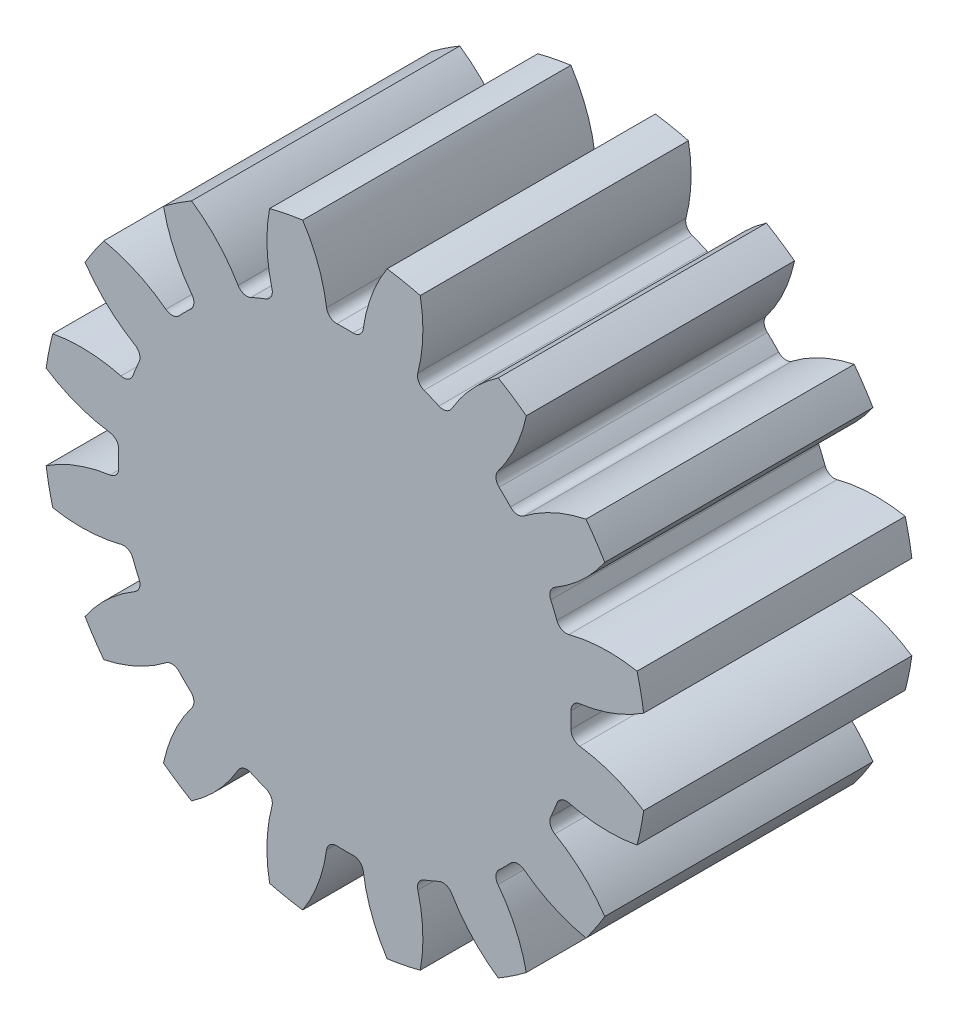
SolidWorks part; units mm, degrees
ref_plane "Front Plane" through (0, 0, 0) normal (0, 0, 1) x (1, 0, 0)
ref_plane "Top Plane" through (0, 0, 0) normal (0, 1, 0) x (1, 0, 0)
ref_plane "Right Plane" through (0, 0, 0) normal (1, 0, 0) x (0, 0, -1)
sketch "Sketch2" plane through (0, 0, 0) normal (0, 0, 1) x (1, 0, 0)
  circle A0 centre (0, 0) radius 10 construction
  circle A1 centre (0, 0) radius 11.25
  dimension "D1" = 20
  dimension "D2" = 22.5
extrude "Boss-Extrude1" add sketch "Sketch2" along normal mid plane 10 contours A1
sketch "Sketch3" plane through (0, 0, 0) normal (0, 0, 1) x (1, 0, 0)
  line L0 (0, 11.25) -> (0, 0) construction
  line L1 (0, 0) -> (4.3052, 10.3936) construction
  line L2 (0, 0) -> (2.1948, 11.0338) construction
  line L3 (-0.6474, 8.4126) -> (0, 0) construction
  line L4 (-0.9802, 9.9518) -> (0.9802, 9.9518) construction
  line L5 (0.9802, 9.9518) -> (2.9028, 9.5694) construction
  line L6 (-1.4199, 11.16) -> (0, 7.2588) construction
  circle A0 centre (0, 0) radius 8.75 construction
  arc A1 (0.6474, 8.4126) -> (-0.6474, 8.4126) centre (0, 0) ccw
  circle A2 centre (0, 0) radius 11.25 construction
  circle A3 centre (0, 0) radius 10 construction
  arc A4 (-1.574, 11.1393) -> (-0.6474, 8.4126) centre (-6.4322, 7.9675) cw
  arc A5 (1.574, 11.1393) -> (0.6474, 8.4126) centre (6.4322, 7.9675) ccw
  arc A6 (1.574, 11.1393) -> (-1.574, 11.1393) centre (0, 0) ccw
  dimension "D4" = 20
  dimension "D1" = 22.5
  dimension "D2" = 2.5
  dimension "D3" = 2.8125
  dimension "D5" = 20
extrude "Cut-Extrude1" cut sketch "Sketch3" against normal through all both and the other way through all
fillet "Fillet1" radius 0.375 2 edges at (0.6474, 8.4126, 0) (-0.6474, 8.4126, 0)
ref_axis "Axis1" through (0, 0, -11) along (0, 0, 1)
pattern_circular "CirPattern1" count 16 over 360 about axis through (0, 0, -11) along (0, 0, 1) of "Cut-Extrude1", "Fillet1"
sketch "Sketch4" plane through (0, 0, -5) normal (0, 0, -1) x (-1, 0, 0)
  line L0 (-1.5, 2) -> (1.5, 2)
  arc A0 (-1.5, 2) -> (1.5, 2) centre (0, 0) ccw
  dimension "D1" = 5
  dimension "D2" = 2
extrude "Cut-Extrude2" cut sketch "Sketch4" against normal blind 9.5
equation "\"Module\"= 1.25mm"
equation "\"Number of teeth\"= 16"
equation "\"pressure angle\"= 20"
equation "\"D1@Sketch2\"=\"Module\"*\"Number of teeth\""
equation "\"D2@Sketch2\"=(\"Number of teeth\"+2) *\"Module\""
equation "\"D1@Sketch3\"=360 /\"Number of teeth\""
equation "\"D2@Sketch3\"=\"Module\"*2"
equation "\"D3@Sketch3\"=\"Module\" *if( \"Module\"=> 1.25,2.25,2.4)"
equation "\"D5@Sketch3\"=\"pressure angle\""
equation "\"D4@Sketch3\"=\"Module\"*\"Number of teeth\""
equation "\"D1@CirPattern1\"=\"Number of teeth\""
equation "\"D1@Fillet1\"=0.3 *\"Module\""
